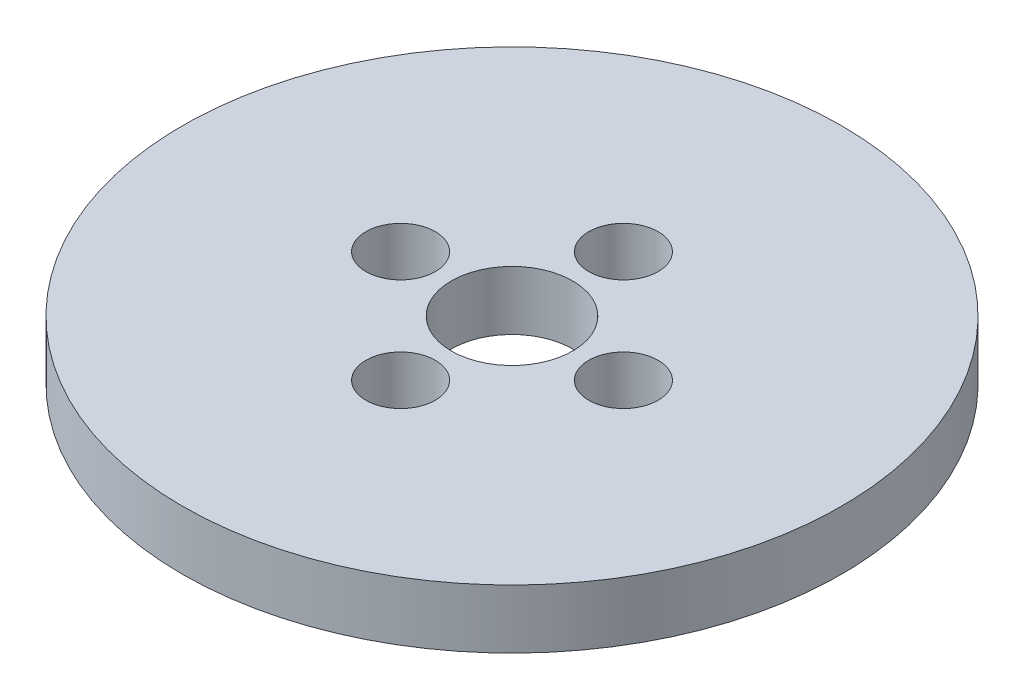
SolidWorks part; units mm, degrees
ref_plane "Front Plane" through (0, 0, 0) normal (0, 0, 1) x (1, 0, 0)
ref_plane "Top Plane" through (0, 0, 0) normal (0, 1, 0) x (1, 0, 0)
ref_plane "Right Plane" through (0, 0, 0) normal (1, 0, 0) x (0, 0, -1)
sketch "Sketch1" plane through (0, 0, 0) normal (0, 1, 0) x (1, 0, 0)
  circle A0 centre (0, 0) radius 95
  dimension "FLANGE_OD" = 190
extrude "Boss-Extrude1" add sketch "Sketch1" along normal blind 17
sketch "Sketch2" plane through (0, 0, 0) normal (0, 1, 0) x (1, 0, 0)
  circle A0 centre (0, 0) radius 17.5
  dimension "BORE_D" = 35
extrude "Cut-Extrude1" cut sketch "Sketch2" along normal through all
sketch "Sketch3" plane through (0, 17, 0) normal (0, 1, 0) x (1, 0, 0)
  circle A0 centre (0, 0) radius 32.1158 construction
  circle A1 centre (-32.1158, 0) radius 10
  dimension "BOLT_D" = 20
  dimension "BOLT_PCD" = 64.2317
extrude "Cut-Extrude2" cut sketch "Sketch3" against normal blind 16.4346
pattern_circular "CirPattern1" count 4 over 360 about axis through (0, 0, 0) along (0, 1, 0) of "Cut-Extrude2"
